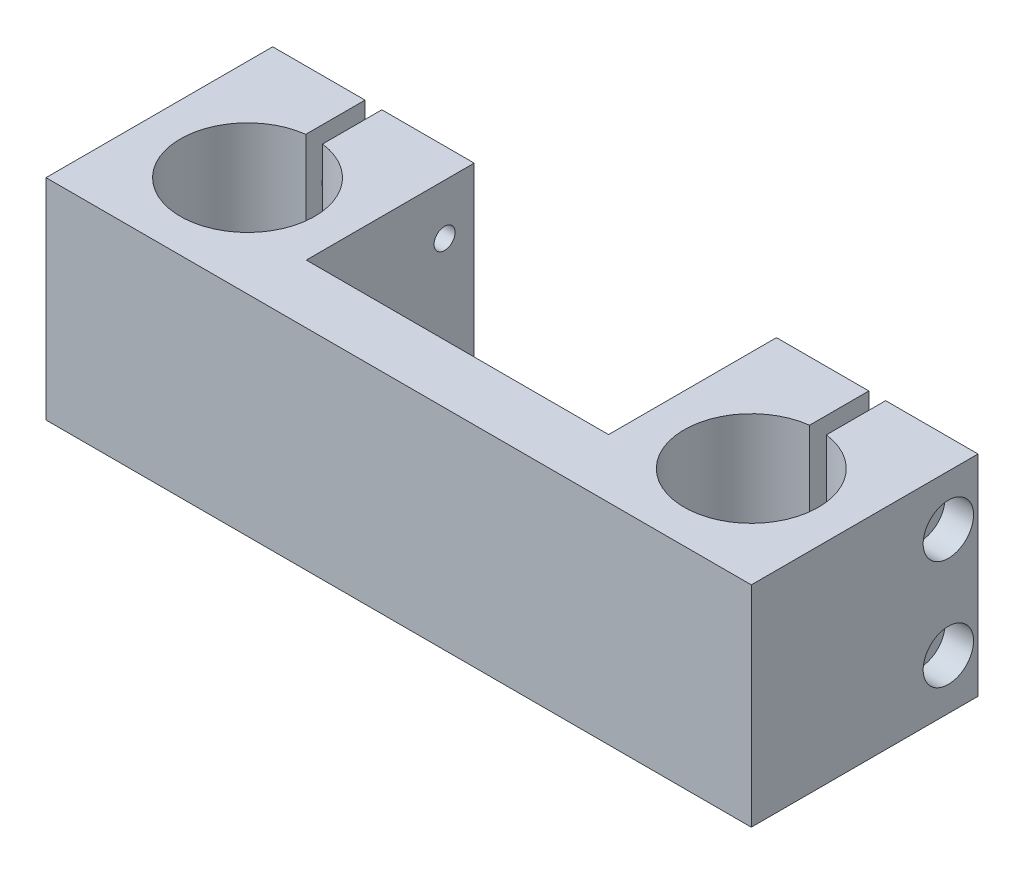
SolidWorks part; units mm, degrees
material "1060 合金"
ref_plane "前视基准面" through (0, 0, 0) normal (0, 0, 1) x (1, 0, 0)
ref_plane "上视基准面" through (0, 0, 0) normal (0, 1, 0) x (1, 0, 0)
ref_plane "右视基准面" through (0, 0, 0) normal (1, 0, 0) x (0, 0, -1)
sketch "草图1" plane through (0, 0, 0) normal (0, 1, 0) x (1, 0, 0)
  line L0 (0, 0) -> (0, 46.9091) construction
  line L1 (-18, 27) -> (-18, 7)
  line L2 (-42, 27) -> (-18, 27)
  line L3 (-42, 27) -> (-42, 0)
  line L4 (-42, 0) -> (42, 0)
  line L5 (42, 27) -> (42, 0)
  line L6 (-42, 27) -> (42, 0) construction
  line L7 (-42, 0) -> (42, 27) construction
  line L8 (-18, 7) -> (18, 7)
  line L9 (18, 7) -> (18, 27)
  line L10 (18, 27) -> (42, 27)
  circle A0 centre (-30, 12) radius 8
  circle A1 centre (30, 12) radius 8
  point P3 (0, 13.5)
  point P18 (-35.4447, 32.0181)
  point P19 (-30.1833, 16.5327)
  dimension "D4" = 16
  dimension "D1" = 12
  dimension "D2" = 12
  dimension "D3" = 36
  dimension "D5" = 60
  dimension "D6" = 15
  dimension "D7" = 20
extrude "凸台-拉伸1" add sketch "草图1" along normal blind 25
sketch "草图2" plane through (0, 25, 0) normal (0, 1, 0) x (1, 0, 0)
  line L0 (0, 0) -> (0, 44.6728) construction
  line L1 (-30, 12) -> (-30, 42.9637) construction
  line L2 (-18, 27) -> (-42, 27) construction
  line L3 (-31, 27) -> (-29, 27)
  line L4 (-31, 27) -> (-31, 19.9373)
  line L5 (-31, 19.9373) -> (-29, 19.9373)
  line L6 (-29, 27) -> (-29, 19.9373)
  line L7 (-31, 27) -> (-29, 19.9373) construction
  line L8 (-31, 19.9373) -> (-29, 27) construction
  circle A0 centre (-30, 12) radius 8 construction
  point P6 (-30, 23.4686)
  dimension "D1" = 2
extrude "切除-拉伸1" cut sketch "草图2" against normal through all
hole_wizard "打孔尺寸(%根据)内六角圆柱头螺钉的类型1" positions "草图4" profile "草图3" counterbore size "M3" standard "GB" end condition up to next
sketch "草图4" plane through (-42, 0, 0) normal (-1, 0, 0) x (0, 0, 1)
  line L0 (-27, 25) -> (0, 25) construction
  line L1 (-27, 0) -> (0, 0) construction
  line L4 (-19.9373, 25) -> (-27, 25) construction
  line L7 (-23.4686, 25) -> (-23.4686, 0) construction
  point P0 (-23.4686, 19)
  point P2 (-23.4686, 6)
  dimension "D1" = 6
  dimension "D2" = 6
sketch "草图3" plane through (-42, 19, -23.4686) normal (0, 1, 0) x (0, 0, 1)
  line L0 (0, 0) -> (0, 71)
  line L1 (0, 71) -> (1.6, 71)
  line L3 (1.6, 71) -> (1.6, 3.4)
  line L4 (1.6, 3.4) -> (3, 3.4)
  line L5 (3, 3.4) -> (3, 0)
  line L7 (3, 0) -> (0, 0)
  line L11 (0, -6.35) -> (0, 107.95) construction
  dimension "通孔孔直径" = 3.2
  dimension "通孔孔深度" = 71
  dimension "柱形沉头孔直径" = 6
  dimension "柱形沉头孔深度" = 3.4
hole_wizard "M3 螺纹孔1" positions "草图6" profile "草图5" tap size "M3" standard "GB" end condition up to next
sketch "草图6" plane through (-18, 0, 0) normal (1, 0, 0) x (0, 0, -1)
  point P0 (23.4686, 19)
  point P3 (23.4686, 6)
sketch "草图5" plane through (-18, 19, -23.4686) normal (0, 1, 0) x (0, 0, -1)
  line L0 (0, 0) -> (0, 11.001)
  line L1 (0, 11.001) -> (1.25, 11.001)
  line L2 (1.25, 11.001) -> (1.25, 0)
  line L5 (1.25, 0) -> (0, 0)
  line L11 (0, -6.35) -> (0, 107.95) construction
  dimension "通孔螺纹孔钻头直径" = 2.5
  dimension "通孔螺纹孔钻头深度" = 11.001
cosmetic thread "孔螺蚊线1" parameters "D2"=3
cosmetic thread "孔螺蚊线2" parameters "D2"=3
mirror "镜向1" about plane through (0, 0, 0) normal (1, 0, 0) of "切除-拉伸1", "M3 螺纹孔1", "打孔尺寸(%根据)内六角圆柱头螺钉的类型1"
